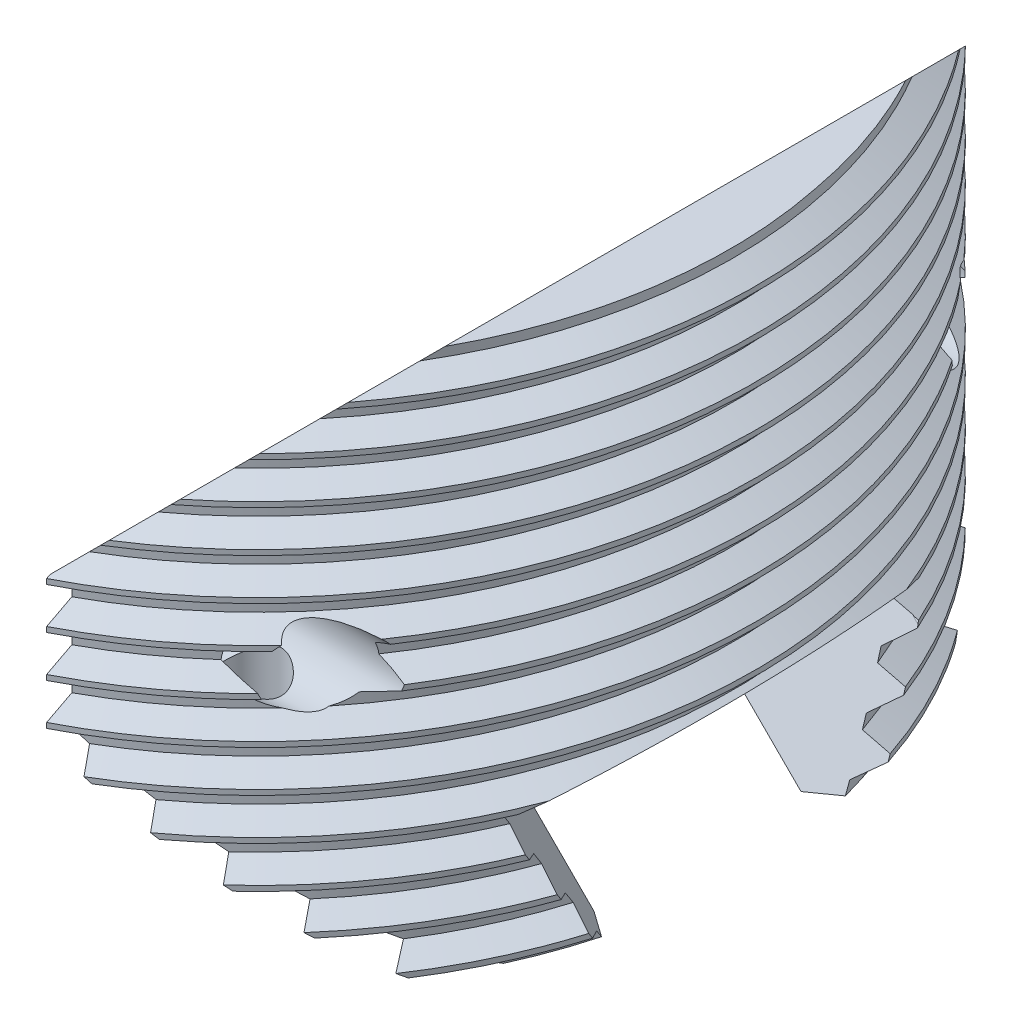
SolidWorks part; units mm, degrees
ref_plane "Front Plane" through (0, 0, 0) normal (0, 0, 1) x (1, 0, 0)
ref_plane "Top Plane" through (0, 0, 0) normal (0, 1, 0) x (1, 0, 0)
ref_plane "Right Plane" through (0, 0, 0) normal (1, 0, 0) x (0, 0, -1)
sketch "Sketch1" plane through (0, 0, 0) normal (0, 1, 0) x (1, 0, 0)
  circle A0 centre (0, 0) radius 25
extrude "Boss-Extrude1" add sketch "Sketch1" along normal blind 28
thread "Thread1" pitch 2.1167 method cut profile "Thread Profile1" start angle 0, offset 5, length 0, pitch 2.1167, diameter 50
ref_plane "Plane1" through (25, -5, 0) normal (0, 0, 1) x (1, 0, 0)
sketch "Thread Profile1" plane through (25, -5, 0) normal (0, 0, 1) x (1, 0, 0)
  line L0 (0, 0) -> (0, 2.1167) construction
  line L11 (0, 0) -> (0, 1.8521)
  line L12 (0, 1.8521) -> (-1.1457, 1.1906)
  line L13 (-1.1457, 1.1906) -> (-1.1457, 0.6615)
  line L15 (-1.1457, 0.6615) -> (0, 0)
  line L17 (-1.1457, 0.926) -> (0, 0.926) construction
  point P2 (0, 0)
  dimension "Pitch" = 2.1167
  dimension "Profile_Angle" = 60
  dimension "Profile_Land" = 0.5292
  dimension "Profile_Height" = 1.1457
sketch "Sketch5" plane through (0, 0, 0) normal (0, 1, 0) x (1, 0, 0)
  line L0 (0, 25) -> (0, -25) construction
  line L1 (0, 0) -> (11, 0) construction
  line L2 (0, 0) -> (21, 0) construction
  line L3 (21, 0) -> (21, 13.5647) construction
  line L4 (21, 13.5647) -> (21, -13.5647) construction
  line L7 (11, 0) -> (11, 22.4499)
  line L8 (11, 0) -> (11, -22.4499)
  circle A0 centre (0, 0) radius 25 construction
  circle A2 centre (0, 0) radius 25 construction
  dimension "D7" = 50
  dimension "D3" = 11
ref_plane "Plane2" through (11, 0, 0) normal (1, 0, 0) x (0, 0, -1)
other "SurfaceCut1"
ref_plane "Plane3" through (0, 28, 0) normal (0, 1, 0) x (1, 0, 0)
ref_plane "Plane4" through (10.5, 10.5, 0) normal (0.7071, 0.7071, 0) x (0, 0, -1)
ref_plane "Plane11" through (10.8536, 10.8536, 0) normal (0.7071, 0.7071, 0) x (0, 0, -1)
sketch "Sketch6" plane through (0, 28, 0) normal (0, 1, 0) x (1, 0, 0)
  line L0 (21, 13.5647) -> (21, -13.5647) construction
  line L1 (21, 0) -> (0, 0) construction
ref_plane "Plane5" through (-3.5, 3.5, 0) normal (0.7071, -0.7071, 0) x (0, 0, 1)
ref_plane "Plane6" through (10.5, -10.5, 0) normal (0.7071, -0.7071, 0) x (0, 0, -1)
other "SurfaceCut2"
other "SurfaceCut3"
sketch "Sketch7" plane through (10.5, -10.5, 0) normal (0.7071, -0.7071, 0) x (0, 0, -1)
  line L0 (0, 14.8492) -> (4.775, 14.8492)
  line L1 (0, 14.8492) -> (13.5647, 14.8492) construction
  line L2 (4.775, 14.8492) -> (10.0783, 20.1525)
  line L4 (-10.0783, 20.1525) -> (-4.775, 14.8492)
  line L5 (13.5647, 14.8492) -> (-13.5647, 14.8492) construction
  line L6 (-4.775, 14.8492) -> (0, 14.8492)
  line L9 (18.2224, 14.8492) -> (-18.2224, 14.8492) construction
  line L10 (-10.0783, 20.1525) -> (0, 20.1525)
  line L11 (0, 34.6482) -> (0, 19.799) construction
  line L12 (0, 20.1525) -> (10.0783, 20.1525)
  dimension "D1" = 7.5
  dimension "D3" = 45
  dimension "D4" = 45
  dimension "D6" = 4.775
extrude "Cut-Extrude1" cut sketch "Sketch7" against normal through all both and the other way through all
ref_plane "Plane7" through (21.6614, -0.1268, -0.1787) normal (-0.9999, 0.0059, 0.0082) x (0.0082, -0.0009, 1)
sketch "Sketch8" plane through (21.6614, -0.1268, -0.1787) normal (-0.9999, 0.0059, 0.0082) x (0.0082, -0.0009, 1)
  line L5 (5.4537, 0.132) -> (10.2512, 6.8506)
  line L6 (10.2512, 6.8506) -> (-9.9063, 6.9968)
  line L7 (5.4537, 0.132) -> (-4.5621, 0.2046)
  line L8 (-4.5621, 0.2046) -> (-9.9063, 6.9968)
extrude "Cut-Extrude2" cut sketch "Sketch8" against normal blind 28 draft 30 draft outward yes
ref_plane "Plane8" through (11, 0, 0) normal (-1, 0, 0) x (0, 0, 1)
sketch "Sketch10" plane through (11, 0, 0) normal (-1, 0, 0) x (0, 0, 1)
  line L0 (0, 0) -> (0, 28.7071) construction
  line L1 (0, 14.3536) -> (25.4236, 14.3536) construction
  line L2 (-16, 14.3536) -> (0, 14.3536)
  line L3 (-16, 18) -> (-16, 10.7071) construction
  line L4 (22.2724, 18) -> (-21.6942, 18) construction
  line L5 (-21.4418, 10.7071) -> (-5.275, 10.7071) construction
  line L6 (16, 18) -> (16, 10.7071) construction
  line L7 (5.275, 10.7071) -> (21.3014, 10.7071) construction
  line L8 (0, 14.3536) -> (16, 14.3536)
  circle A0 centre (-16, 14.3536) radius 1.25
  circle A1 centre (16, 14.3536) radius 1.25
  point P17 (16, 14.3536)
  dimension "D1" = 2.5
  dimension "D2" = 16
hole_wizard "Tap Drill for M5x0.8 Tap2" positions "Sketch25" profile "Sketch26" hole size "M5x0.8" standard "ANSI Metric" end condition through all
sketch "Sketch25" plane through (11, 0, 0) normal (-1, 0, 0) x (0, 0, 1)
  point P0 (-16, 14.3536)
  point P3 (16, 14.3536)
sketch "Sketch26" plane through (11, 14.3536, -16) normal (0, 1, 0) x (0, 0, 1)
  line L0 (0, 0) -> (0, 14.0558)
  line L1 (0, 14.0558) -> (2.1, 14.0558)
  line L2 (2.1, 14.0558) -> (2.1, 0)
  line L5 (2.1, 0) -> (0, 0)
  line L11 (0, -6.35) -> (0, 107.95) construction
  dimension "Thru Hole Dia." = 4.2
  dimension "Thru Hole Depth" = 14.0558
ref_plane "Plane9" through (0, 28, 0) normal (0, 1, 0) x (1, 0, 0)
sketch "Sketch28" plane through (0, 28, 0) normal (0, 1, 0) x (1, 0, 0)
  line L0 (11, 0) -> (11, 16)
  line L1 (11, 0) -> (11, 22.4499) construction
  line L2 (11, 0) -> (11, -16)
  line L3 (11, 0) -> (11, -22.4499) construction
  line L4 (11, 16) -> (11, 0) construction
  line L5 (11, 16) -> (15, 16)
  line L6 (11, -16) -> (15, -16)
  circle A0 centre (15, 16) radius 1.5
  circle A1 centre (15, -16) radius 1.5
  dimension "D1" = 4
extrude "Cut-Extrude3" cut sketch "Sketch28" against normal through all both and the other way through all contours A1 | A0
ref_plane "Plane10" through (11.0303, 11.0303, 0) normal (-0.7071, -0.7071, 0) x (-0.7071, 0.7071, 0)
